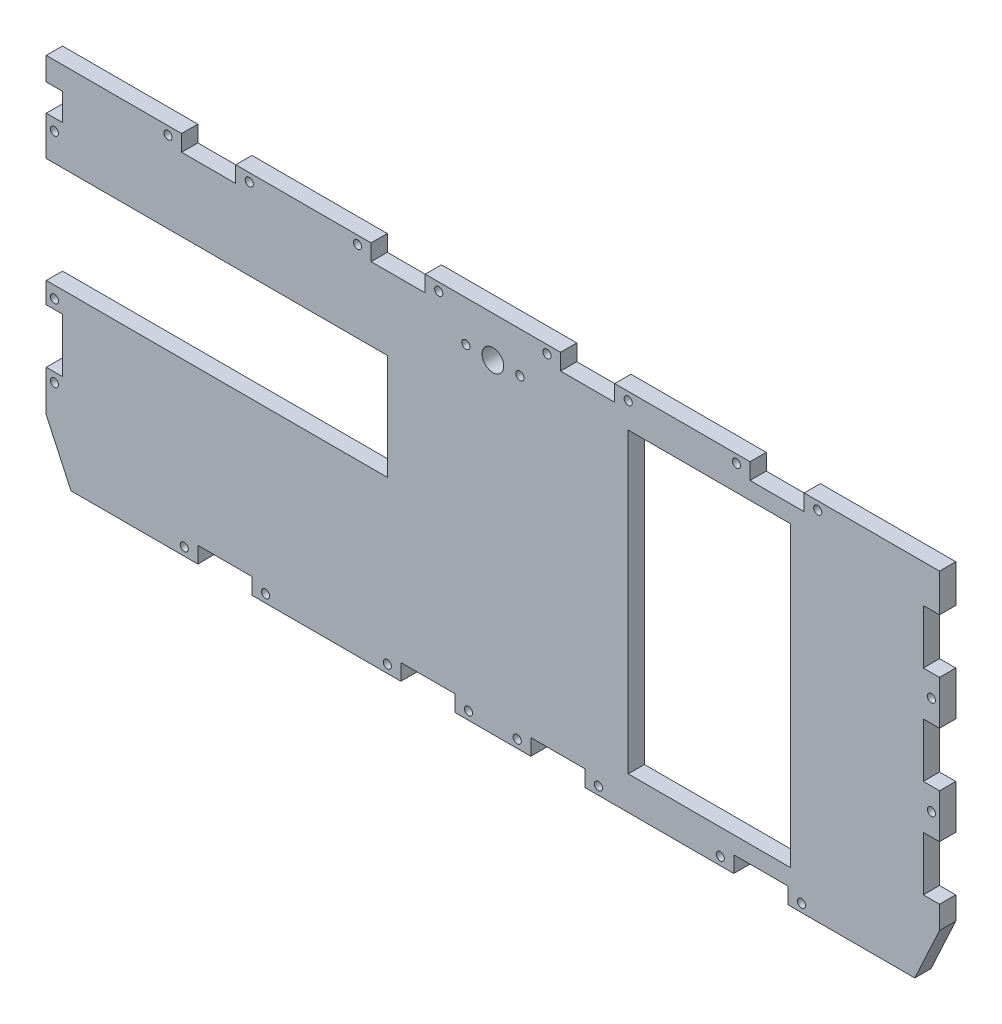
SolidWorks part; units mm, degrees
ref_plane "Plan de face" through (0, 0, 0) normal (0, 0, 1) x (1, 0, 0)
ref_plane "Plan de dessus" through (0, 0, 0) normal (0, 1, 0) x (1, 0, 0)
ref_plane "Plan de droite" through (0, 0, 0) normal (1, 0, 0) x (0, 0, -1)
sketch "Esquisse1" plane through (0, 0, 0) normal (0, 0, 1) x (1, 0, 0)
  line L0 (0, 124.9429) -> (0, -204.46) construction
  line L1 (-165, 96.73) -> (165, 96.73)
  line L2 (165, 96.73) -> (165, -18.27)
  line L3 (165, -18.27) -> (123, -109.0224)
  line L4 (123, -109.0224) -> (-123, -109.0224)
  line L5 (-211.9802, 0) -> (248.5953, 0) construction
  line L6 (-123, -109.0224) -> (-165, -18.27)
  line L7 (-165, -18.27) -> (-165, 96.73)
  dimension "D2" = 165
  dimension "D3" = 330
  dimension "D4" = 100
  dimension "D5" = 115
  dimension "D6" = 100
  dimension "D7" = 246
  dimension "D8" = 205.7524
  dimension "D9" = 96.73
  dimension "D10" = 115
extrude "Boss.-Extru.1" add sketch "Esquisse1" along normal blind 6
sketch "Esquisse3" plane through (0, 0, 0) normal (0, 0, -1) x (-1, 0, 0)
  line L0 (165, 96.73) -> (165, -18.27) construction
  line L1 (165, -3.06) -> (159, -3.06)
  line L2 (165, -3.06) -> (165, 16.94)
  line L3 (165, 16.94) -> (159, 16.94)
  line L4 (159, -3.06) -> (159, 16.94)
  line L5 (123, -109.0224) -> (-123, -109.0224) construction
  line L6 (165, 78.2326) -> (159, 78.2326)
  line L7 (165, 78.2326) -> (165, 88.2326)
  line L8 (165, 88.2326) -> (159, 88.2326)
  line L9 (159, 78.2326) -> (159, 88.2326)
  line L10 (-14, -38.02) -> (-14, -32.02)
  line L11 (109, -38.02) -> (89, -38.02)
  line L12 (109, -38.02) -> (109, -32.02)
  line L13 (109, -32.02) -> (89, -32.02)
  line L15 (0, -209.4812) -> (0, 177.1799) construction
  line L16 (-110, 84.355) -> (-50, 84.355)
  line L17 (-165, 82.73) -> (-159, 82.73)
  line L18 (89, -38.02) -> (89, -32.02)
  line L19 (34, -38.02) -> (14, -38.02)
  line L20 (34, -38.02) -> (34, -32.02)
  line L21 (34, -32.02) -> (14, -32.02)
  line L22 (-165, 82.73) -> (-165, 62.73)
  line L23 (-165, 62.73) -> (-159, 62.73)
  line L24 (-159, 82.73) -> (-159, 62.73)
  line L25 (-165, 46.44) -> (-159, 46.44)
  line L26 (-165, 46.44) -> (-165, 26.44)
  line L27 (-165, 26.44) -> (-159, 26.44)
  line L28 (-159, 46.44) -> (-159, 26.44)
  line L29 (-165, 10.15) -> (-159, 10.15)
  line L30 (-165, 96.73) -> (165, 96.73) construction
  line L31 (115, 96.73) -> (95, 96.73)
  line L32 (115, 96.73) -> (115, 90.73)
  line L33 (115, 90.73) -> (95, 90.73)
  line L34 (95, 96.73) -> (95, 90.73)
  line L35 (-25, 96.73) -> (-25, 90.73)
  line L36 (45, 96.73) -> (25, 96.73)
  line L37 (45, 96.73) -> (45, 90.73)
  line L38 (45, 90.73) -> (25, 90.73)
  line L39 (25, 96.73) -> (25, 90.73)
  line L40 (-45, 90.73) -> (-25, 90.73)
  line L41 (-45, 96.73) -> (-45, 90.73)
  line L42 (-45, 96.73) -> (-25, 96.73)
  line L43 (-95, 96.73) -> (-95, 90.73)
  line L44 (-115, 90.73) -> (-95, 90.73)
  line L45 (-115, 96.73) -> (-115, 90.73)
  line L46 (-115, 96.73) -> (-95, 96.73)
  line L47 (-165, 10.15) -> (-165, -9.85)
  line L48 (14, -38.02) -> (14, -32.02)
  line L49 (-34, -32.02) -> (-14, -32.02)
  line L50 (-34, -38.02) -> (-34, -32.02)
  line L51 (-34, -38.02) -> (-14, -38.02)
  line L52 (-165, -9.85) -> (-159, -9.85)
  line L53 (165, 63.73) -> (39, 63.73)
  line L54 (165, 63.73) -> (165, 24.73)
  line L55 (165, 24.73) -> (39, 24.73)
  line L56 (-159, 10.15) -> (-159, -9.85)
  line L57 (-89, -38.02) -> (-89, -32.02)
  line L58 (-109, -32.02) -> (-89, -32.02)
  line L59 (-109, -38.02) -> (-109, -32.02)
  line L60 (-109, -38.02) -> (-89, -38.02)
  line L62 (-110, 84.355) -> (-110, -25.645)
  line L63 (-110, -25.645) -> (-50, -25.645)
  line L64 (-50, 84.355) -> (-50, -25.645)
  line L65 (-165, -18.27) -> (-165, 96.73) construction
  line L66 (39, 63.73) -> (39, 24.73)
  dimension "D1" = 20
  dimension "D2" = 6
  dimension "D3" = 6
  dimension "D4" = 10
  dimension "D5" = 6
  dimension "D6" = 20
  dimension "D7" = 60
  dimension "D8" = 55
  dimension "D9" = 8.4974
  dimension "D10" = 20
  dimension "D11" = 20
  dimension "D12" = 50
  dimension "D13" = 50
  dimension "D14" = 6
  dimension "D15" = 110
  dimension "D16" = 56
  dimension "D17" = 55
  dimension "D18" = 20
  dimension "D19" = 20
  dimension "D20" = 20
  dimension "D21" = 6
  dimension "D22" = 6
  dimension "D23" = 20
  dimension "D24" = 71.0024
  dimension "D25" = 71.0024
  dimension "D26" = 33
  dimension "D27" = 39
  dimension "D28" = 126
  dimension "D29" = 6.375
  dimension "D30" = 15.21
  dimension "D31" = 6
  dimension "D32" = 6
  dimension "D33" = 6
  dimension "D34" = 14
  dimension "D35" = 16.29
  dimension "D36" = 16.29
extrude "Enlèv. mat.-Extru.2" cut sketch "Esquisse3" against normal blind 6
sketch "Esquisse4" plane through (0, 0, 0) normal (0, 0, -1) x (-1, 0, 0)
  line L0 (159, 78.2326) -> (165, 78.2326) construction
  line L1 (115, 90.73) -> (115, 96.73) construction
  line L2 (120.102, -35.02) -> (4.7601, -35.02) construction
  line L3 (14, -32.02) -> (14, -38.02) construction
  line L4 (34, -38.02) -> (34, -32.02) construction
  line L5 (89, -32.02) -> (89, -38.02) construction
  line L6 (26.5287, 81.73) -> (-31.7243, 81.73) construction
  line L7 (109, -38.02) -> (109, -32.02) construction
  line L8 (165, 78.2326) -> (165, 63.73) construction
  line L9 (-120.102, -35.02) -> (-4.7601, -35.02) construction
  line L10 (-25, 96.73) -> (25, 96.73) construction
  line L11 (143.8632, 93.73) -> (-5, 93.73) construction
  line L12 (45, 96.73) -> (95, 96.73) construction
  line L13 (-162, -27.3544) -> (-162, 100.425) construction
  line L14 (95, 96.73) -> (95, 90.73) construction
  line L15 (45, 90.73) -> (45, 96.73) construction
  line L16 (25, 96.73) -> (25, 90.73) construction
  line L17 (0, 142.2997) -> (0, -202.2086) construction
  line L18 (-165, -18.27) -> (-165, -9.85) construction
  line L19 (-80, 84.355) -> (-80, -25.645) construction
  line L21 (165, 16.94) -> (159, 16.94) construction
  line L22 (162, -8.8216) -> (162, 103.5789) construction
  line L25 (-50, 84.355) -> (-110, 84.355) construction
  line L26 (-110, -25.645) -> (-50, -25.645) construction
  line L27 (-159, 46.44) -> (-165, 46.44) construction
  line L28 (-165, 26.44) -> (-159, 26.44) construction
  line L31 (159, -3.06) -> (165, -3.06) construction
  circle A0 centre (162, 20.335) radius 1.5
  circle A1 centre (114, -35.02) radius 1.5
  circle A2 centre (162, 73.9826) radius 1.5
  circle A3 centre (84, -35.02) radius 1.5
  circle A4 centre (39, -35.02) radius 1.5
  circle A5 centre (162, -6.46) radius 1.5
  circle A6 centre (9, -35.02) radius 1.5
  circle A7 centre (-9, -35.02) radius 1.5
  circle A8 centre (-39, -35.02) radius 1.5
  circle A9 centre (-84, -35.02) radius 1.5
  circle A10 centre (120, 93.73) radius 1.5
  circle A11 centre (-114, -35.02) radius 1.5
  circle A12 centre (90, 93.73) radius 1.5
  circle A13 centre (0, 81.73) radius 4
  circle A14 centre (50, 93.73) radius 1.5
  circle A15 centre (20, 93.73) radius 1.5
  circle A16 centre (-162, 18.29) radius 1.5
  circle A17 centre (-162, 54.585) radius 1.5
  circle A18 centre (-20, 93.73) radius 1.5
  circle A19 centre (-50, 93.73) radius 1.5
  circle A20 centre (-90, 93.73) radius 1.5
  circle A21 centre (-120, 93.73) radius 1.5
  circle A22 centre (-10, 81.73) radius 1.5
  circle A23 centre (10, 81.73) radius 1.5
  dimension "D3" = 3
  dimension "D10" = 3
  dimension "D11" = 3
  dimension "D12" = 3
  dimension "D13" = 5
  dimension "D14" = 5
  dimension "D18" = 3
  dimension "D19" = 3
  dimension "D29" = 3
  dimension "D30" = 8.15
  dimension "D31" = 3
  dimension "D32" = 10
  dimension "D33" = 3
  dimension "D34" = 3
  dimension "D35" = 10
  dimension "D40" = 5
  dimension "D5" = 3.395
  dimension "D8" = 5
  dimension "D15" = 5
  dimension "D16" = 5
  dimension "D20" = 3.4
  dimension "D17" = 3
  dimension "D21" = 3
  dimension "D22" = 3
  dimension "D23" = 3
  dimension "D25" = 8
  dimension "D27" = 8.145
  dimension "D9" = 3
  dimension "D7" = 3
  dimension "D24" = 3
  dimension "D6" = 4.25
  dimension "D26" = 3
  dimension "D28" = 3
  dimension "D36" = 15
  dimension "D38" = 5
  dimension "D42" = 5
extrude "Enlèv. mat.-Extru.3" cut sketch "Esquisse4" against normal blind 6
sketch "Esquisse5" plane through (0, 0, 0) normal (0, 0, -1) x (-1, 0, 0)
  line L0 (45, 96.73) -> (95, 96.73) construction
  line L1 (209.7155, -38.02) -> (-246.3297, -38.02)
  line L2 (209.7155, -38.02) -> (209.7155, -174.249)
  line L3 (209.7155, -174.249) -> (-246.3297, -174.249)
  line L4 (-246.3297, -38.02) -> (-246.3297, -174.249)
  dimension "D1" = 134.75
extrude "Enlèv. mat.-Extru.4" cut sketch "Esquisse5" against normal blind 6
